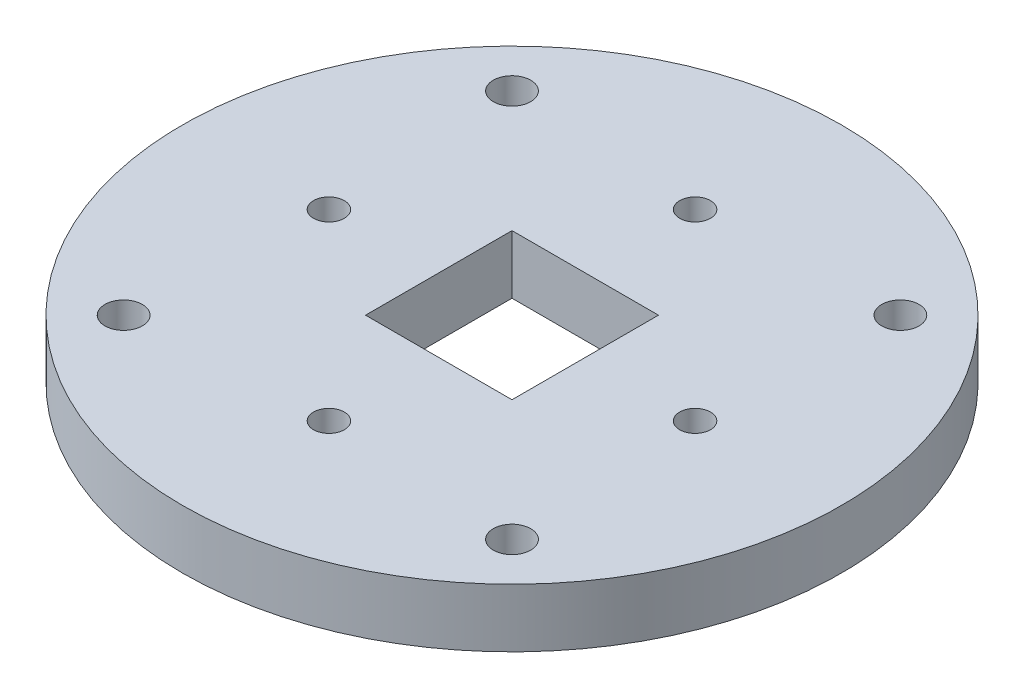
SolidWorks part; units mm, degrees
ref_plane "Front Plane" through (0, 0, 0) normal (0, 0, 1) x (1, 0, 0)
ref_plane "Top Plane" through (0, 0, 0) normal (0, 1, 0) x (1, 0, 0)
ref_plane "Right Plane" through (0, 0, 0) normal (1, 0, 0) x (0, 0, -1)
sketch "Sketch1" plane through (0, 0, 0) normal (0, 1, 0) x (1, 0, 0)
  circle A0 centre (0, 0) radius 45
  dimension "D1" = 90
extrude "Boss-Extrude1" add sketch "Sketch1" along normal blind 8
sketch "Sketch3" plane through (0, 8, 0) normal (0, 1, 0) x (1, 0, 0)
  line L0 (0, -1000) -> (0, 49000) construction
  circle A0 centre (0, 25) radius 2.1
  dimension "D1" = 4.2
  dimension "D2" = 25
extrude "Cut-Extrude2" cut sketch "Sketch3" against normal through all
pattern_circular "CirPattern1" count 4 over 360 about axis through (0, 8, 0) along (0, -1, 0) of "Cut-Extrude2"
sketch "Sketch4" plane through (0, 8, 0) normal (0, 1, 0) x (1, 0, 0)
  line L1 (-10, -10) -> (10, -10)
  line L2 (-10, -10) -> (-10, 10)
  line L3 (-10, 10) -> (10, 10)
  line L4 (10, -10) -> (10, 10)
  line L5 (-10, -10) -> (10, 10) construction
  line L6 (-10, 10) -> (10, -10) construction
  point P0 (0, 0)
  dimension "D1" = 20
  dimension "D2" = 20
extrude "Cut-Extrude3" cut sketch "Sketch4" against normal blind 10
sketch "Sketch6" plane through (0, 8, 0) normal (0, 1, 0) x (1, 0, 0)
  line L0 (-707.1068, -707.1068) -> (34648.2323, 34648.2323) construction
  line L1 (-707.1068, 707.1068) -> (34648.2323, -34648.2323) construction
  line L2 (-1000, 0) -> (49000, 0) construction
  circle A0 centre (0, 0) radius 37.5 construction
  circle A1 centre (-26.5165, 26.5165) radius 2.55
  circle A2 centre (26.5165, 26.5165) radius 2.55
  circle A3 centre (26.5165, -26.5165) radius 2.55
  circle A4 centre (-26.5165, -26.5165) radius 2.55
  circle A5 centre (0, 0) radius 45 construction
  dimension "D1" = 7.5
  dimension "D2" = 5.1
  dimension "D3" = 5.1
  dimension "D4" = 5.1
  dimension "D5" = 5.1
  dimension "D6" = 45
  dimension "D7" = 45
extrude "Cut-Extrude4" cut sketch "Sketch6" against normal through all
